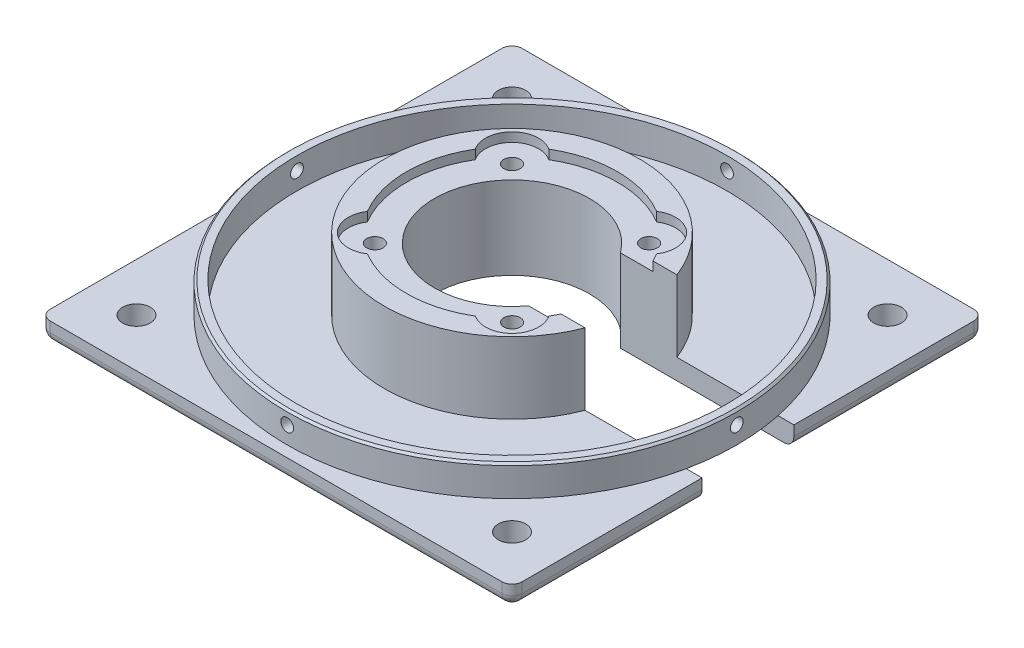
SolidWorks part; units mm, degrees
ref_plane "Front Plane" through (0, 0, 0) normal (0, 0, 1) x (1, 0, 0)
ref_plane "Top Plane" through (0, 0, 0) normal (0, 1, 0) x (1, 0, 0)
ref_plane "Right Plane" through (0, 0, 0) normal (1, 0, 0) x (0, 0, -1)
sketch "Sketch3" plane through (0, 0, 0) normal (0, 1, 0) x (1, 0, 0)
  circle A0 centre (0, 0) radius 7.6
  circle A1 centre (0, 0) radius 12.5
  dimension "D1" = 15.2
  dimension "D2" = 25
extrude "Boss-Extrude2" add sketch "Sketch3" along normal blind 9
sketch "Sketch4" plane through (0, 9, 0) normal (0, 1, 0) x (1, 0, 0)
  line L0 (6.1245, 4.5) -> (6.1245, -4.5)
  line L1 (6.1245, -4.5) -> (13.2817, -4.5)
  line L2 (13.2817, -4.5) -> (13.2817, 4.5)
  line L3 (13.2817, 4.5) -> (6.1245, 4.5)
  circle A0 centre (0, 0) radius 7.6 construction
  point P0 (0, 0)
  point P1 (6.1245, 4.5)
  point P3 (6.1245, -4.5)
  dimension "D1" = 4.5
extrude "Cut-Extrude2" cut sketch "Sketch4" against normal blind 9
sketch "Sketch5" plane through (0, 9, 0) normal (0, 1, 0) x (1, 0, 0)
  line L0 (0, 0) -> (17.4279, 0) construction
  line L1 (0, 0) -> (-11.2462, -11.2462) construction
  line L2 (0, 0) -> (-11.0539, 11.0539) construction
  point P0 (0, 0)
  point P1 (-6.715, 6.72)
  point P3 (-6.715, -6.72)
  point P9 (6.72, -6.715)
  point P10 (6.72, 6.715)
  dimension "D1" = 6.72
  dimension "D2" = 9.5
  dimension "D3" = 6.72
  dimension "D4" = 9.5
sketch "Sketch6" plane through (0, 9, 0) normal (0, 1, 0) x (1, 0, 0)
  line L0 (0, 0) -> (-11.2462, -11.2462) construction
  line L1 (0, 0) -> (-11.0539, 11.0539) construction
  line L2 (0, 0) -> (17.4279, 0) construction
  point P0 (5.2883, -8.8853)
  point P9 (-8.8853, 5.2883)
  point P12 (5.2883, 8.8853)
  point P14 (8.8893, -5.2817)
  point P15 (-5.2817, 8.8893)
  point P16 (8.8893, 5.2817)
  point P17 (-5.2817, -8.8893)
  point P18 (-8.8853, -5.2883)
  dimension "D1" = 2.6
  dimension "D2" = 10.34
  dimension "D3" = 2.6
  dimension "D4" = 10.34
sketch "Sketch8" plane through (0, 9, 0) normal (0, 1, 0) x (1, 0, 0)
  circle A0 centre (0, 0) radius 10.34
extrude "Cut-Extrude5" cut sketch "Sketch8" against normal blind 0.9
hole_wizard "Tap Drill for M2x0.4 Tap1" positions "3DSketch1" profile "Sketch10" hole size "M2x0.4" standard "ANSI Metric" end condition through all
sketch3d "3DSketch1"
  point P0 (6.72, 9, 6.715)
  point P3 (-6.715, 9, 6.72)
  point P6 (-6.715, 9, -6.72)
  point P9 (6.72, 9, -6.715)
sketch "Sketch10" plane through (6.72, 9, 6.715) normal (1, 0, 0) x (0, 0, 1)
  line L0 (0, 0) -> (0, 9)
  line L1 (0, 9) -> (0.8, 9)
  line L2 (0.8, 9) -> (0.8, 0)
  line L5 (0.8, 0) -> (0, 0)
  line L11 (0, -6.35) -> (0, 107.95) construction
  dimension "Thru Hole Dia." = 1.6
  dimension "Thru Hole Depth" = 9
sketch "Sketch11" plane through (0, 9, 0) normal (0, 1, 0) x (1, 0, 0)
  line L0 (8.8893, 5.2817) -> (5.2883, 8.8853)
  line L1 (8.8893, -5.2817) -> (5.2883, -8.8853)
  line L2 (-5.2817, -8.8893) -> (-8.8853, -5.2883)
  line L3 (-5.2817, 8.8893) -> (-8.8853, 5.2883)
  arc A0 (5.2883, -8.8853) -> (8.8893, -5.2817) centre (6.72, -6.715) ccw
  arc A1 (9.3094, 4.5) -> (9.3094, -4.5) centre (0, 0) ccw construction
  arc A2 (8.8893, 5.2817) -> (5.2883, 8.8853) centre (6.72, 6.715) ccw
  arc A3 (-5.2817, 8.8893) -> (-8.8853, 5.2883) centre (-6.715, 6.72) ccw
  arc A4 (-8.8853, -5.2883) -> (-5.2817, -8.8893) centre (-6.715, -6.72) ccw
extrude "Cut-Extrude6" cut sketch "Sketch11" against normal blind 0.9
sketch "Sketch12" plane through (0, 0, 0) normal (0, -1, 0) x (1, 0, 0)
  line L0 (0, 0) -> (17.7684, 0) construction
  line L1 (0, 0) -> (0, 18.0241) construction
  line L2 (23.125, -23.125) -> (-23.125, -23.125)
  line L3 (-23.125, -23.125) -> (-23.125, 23.125)
  line L4 (-23.125, 23.125) -> (23.125, 23.125)
  line L9 (6.4622, 4) -> (23.125, 4)
  line L11 (23.125, -4.5) -> (6.1245, -4.5)
  line L13 (23.125, -23.125) -> (23.125, -4.5)
  line L14 (23.125, 23.125) -> (23.125, 4)
  arc A0 (6.1245, -4.5) -> (6.4622, 4) centre (0, 0) cw
  circle A1 centre (0, 0) radius 7.6 construction
  point P0 (23.125, -23.125)
  point P4 (23.125, 23.125)
  point P5 (-23.125, 23.125)
  point P7 (-23.125, -23.125)
  dimension "D1" = 23.125
  dimension "D2" = 23.125
extrude "Boss-Extrude4" add sketch "Sketch12" against normal blind 2
fillet "Fillet2" radius 1 2 edges at (-23.125, 0, 0) (0, 0, 23.125)
fillet "Fillet3" radius 1 2 edges at (-22.8321, 0.2929, 22.8321) (-23.125, 1.5, 23.125)
sketch "Sketch13" plane through (0, 0, 0) normal (0, -1, 0) x (1, 0, 0)
  line L0 (0, 0) -> (-25.0462, 0) construction
  line L1 (0, 0) -> (0, 26.5218) construction
  point P0 (18.3989, -18.3989)
  point P5 (18.3989, 18.3989)
  point P6 (-18.3989, -18.3989)
  point P7 (-18.3989, 18.3989)
  dimension "D1" = 18.3989
  dimension "D2" = 18.3989
hole_wizard "M2.5 Clearance Hole1" positions "3DSketch2" profile "Sketch14" hole size "M2.5" standard "ANSI Metric" end condition through all
sketch3d "3DSketch2"
  point P0 (18.3989, 0, 18.3989)
  point P3 (18.3989, 0, -18.3989)
  point P6 (-18.3989, 0, -18.3989)
  point P9 (-18.3989, 0, 18.3989)
sketch "Sketch14" plane through (18.3989, 0, 18.3989) normal (1, 0, 0) x (0, 0, -1)
  line L0 (0, 0) -> (0, 9)
  line L1 (0, 9) -> (1.35, 9)
  line L2 (1.35, 9) -> (1.35, 0)
  line L5 (1.35, 0) -> (0, 0)
  line L11 (0, -6.35) -> (0, 107.95) construction
  dimension "Thru Hole Dia." = 2.7
  dimension "Thru Hole Depth" = 9
fillet "Fillet4" radius 1 7 edges at (23.125, 1.5, 23.125) (23.125, 0.2929, 22.8321) (-23.125, 1.5, -23.125) (-22.8321, 0.2929, -23.125) (23.125, 0, 13.0625) (23.125, 0, -13.8125) (0.5, 0, -23.125)
fillet "Fillet5" radius 1 2 edges at (22.8321, 0.2929, -22.8321) (23.125, 1.5, -23.125)
sketch "Sketch15" plane through (0, 2, 0) normal (0, 1, 0) x (1, 0, 0)
  circle A0 centre (0, 0) radius 22.0375
  circle A1 centre (0, 0) radius 21.075
  point P0 (0, 0)
extrude "Boss-Extrude6" add sketch "Sketch15" along normal blind 3
hole_wizard "Tap Drill for M1.6x0.35 Tap1" positions "3DSketch4" profile "Sketch25" hole size "M1.6x0.35" standard "ANSI Metric" end condition up to next
sketch3d "3DSketch4"
  point P0 (22.0375, 3.7, 0)
sketch "Sketch25" plane through (22.0375, 3.7, 0) normal (0, 1, 0) x (0, 0, -1)
  line L0 (0, 0) -> (0, 0.9625)
  line L1 (0, 0.9625) -> (0.625, 0.9625)
  line L2 (0.625, 0.9625) -> (0.625, 0)
  line L5 (0.625, 0) -> (0, 0)
  line L11 (0, -6.35) -> (0, 107.95) construction
  dimension "Thru Hole Dia." = 1.25
  dimension "Thru Hole Depth" = 0.9625
ref_axis "Axis1" through (0, 8.1, 0) along (0, -1, 0)
pattern_circular "CirPattern1" count 4 over 360 about axis through (0, 8.1, 0) along (0, -1, 0) of "Tap Drill for M1.6x0.35 Tap1"
chamfer "Chamfer1" distance 0.2 angle 45 1 edges at (0, 5, 22.0375)
sketch "Sketch26" plane through (0, 2, 0) normal (0, 1, 0) x (1, 0, 0)
  line L1 (6.1245, -4.5) -> (23.125, -4.5)
  line L2 (6.1245, -4.5) -> (6.1245, 4.5)
  line L3 (6.1245, 4.5) -> (23.125, 4.5)
  line L4 (23.125, -4.5) -> (23.125, 4.5)
extrude "Cut-Extrude7" cut sketch "Sketch26" against normal up to next
